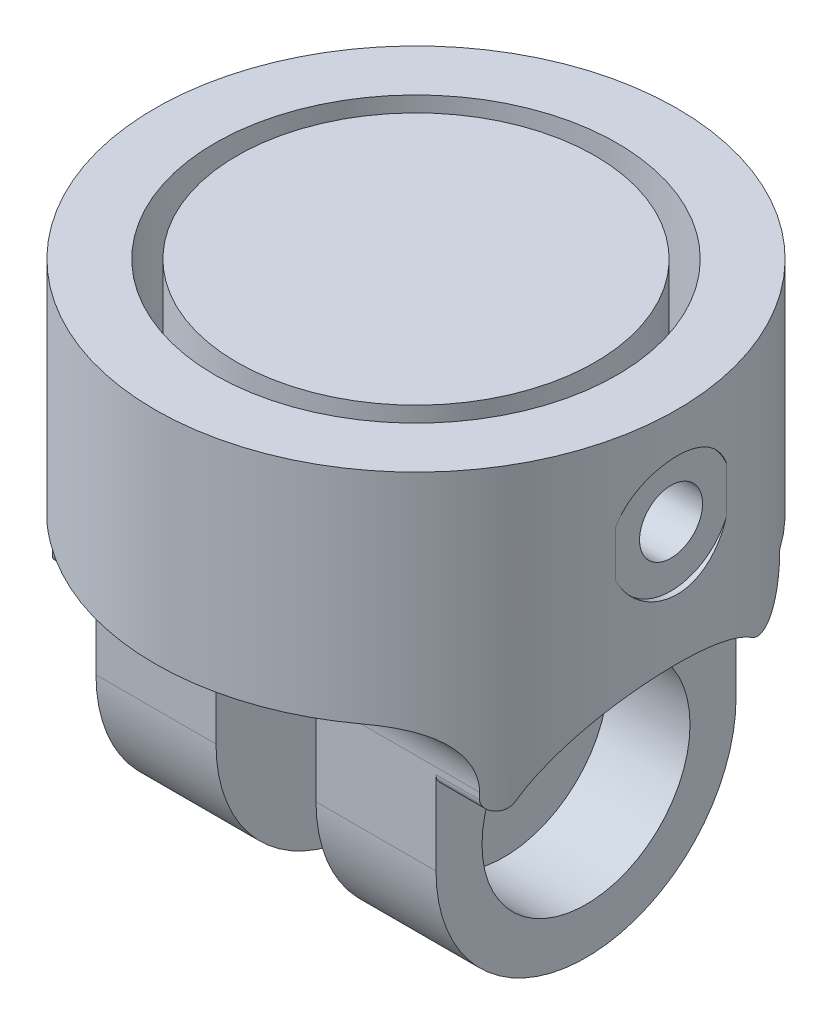
SolidWorks part; units mm, degrees
material "PLA Black"
ref_plane "Front" through (0, 0, 0) normal (0, 0, 1) x (1, 0, 0)
ref_plane "Top" through (0, 0, 0) normal (0, 1, 0) x (1, 0, 0)
ref_plane "Right" through (0, 0, 0) normal (1, 0, 0) x (0, 0, -1)
sketch "Sketch1" plane through (0, 0, 0) normal (0, 1, 0) x (1, 0, 0)
  line L0 (0, 8.95) -> (0, 10.05) construction
  circle A0 centre (0, 0) radius 10.05
  circle A1 centre (0, 0) radius 13.05
  circle A2 centre (0, 0) radius 9.5 construction
  circle A4 centre (0, 0) radius 8.95
  point P11 (0, 9.5)
  dimension "D1" = 1.1
  dimension "D2" = 3
  dimension "D3" = 19
extrude "Boss-Extrude1" add sketch "Sketch1" along normal blind 10 contours A1 A0 | A4 region at (-12.6809, 0, 0) region at (0, 0, 0)
sketch "Sketch3" plane through (0, 0, 0) normal (0, -1, 0) x (1, 0, 0)
  circle A2 centre (0, 0) radius 13.05 construction
  circle A3 centre (0, 0) radius 13.05
extrude "Boss-Extrude2" add sketch "Sketch3" along normal blind 1
sketch "Sketch4" plane through (0, -1, 0) normal (0, -1, 0) x (1, 0, 0)
  line L0 (0, 17.8908) -> (0, -17.0763) construction
  line L1 (2.5, 7.5) -> (8.5, 7.5)
  line L2 (2.5, 7.5) -> (2.5, -7.5)
  line L3 (2.5, -7.5) -> (8.5, -7.5)
  line L4 (8.5, 7.5) -> (8.5, -7.5)
  line L5 (-8.5, 7.5) -> (-8.5, -7.5)
  line L6 (-2.5, -7.5) -> (-8.5, -7.5)
  line L7 (-2.5, 7.5) -> (-2.5, -7.5)
  line L8 (-2.5, 7.5) -> (-8.5, 7.5)
  line L9 (16.8049, 0) -> (-19.8998, 0) construction
  dimension "D1" = 6
  dimension "D2" = 5
  dimension "D3" = 15
extrude "Boss-Extrude3" add sketch "Sketch4" along normal blind 15
sketch "Sketch5" plane through (8.5, 0, 0) normal (1, 0, 0) x (0, 0, -1)
  line L0 (-7.5, -16) -> (-7.5, -1) construction
  line L1 (7.5, -16) -> (7.5, -1) construction
  line L2 (7.5, -8.5) -> (7.5, -17.1619)
  line L3 (7.5, -17.1619) -> (-7.5, -17.1619)
  line L4 (-7.5, -17.1619) -> (-7.5, -8.5)
  arc A0 (-7.5, -8.5) -> (7.5, -8.5) centre (0, -8.5) ccw
  circle A1 centre (0, -8.5) radius 1.55
  dimension "D1" = 3.1
extrude "Cut-Extrude1" cut sketch "Sketch5" against normal through all both and the other way through all
sketch "Sketch6" plane through (8.5, 0, 0) normal (1, 0, 0) x (0, 0, -1)
  circle A0 centre (0, -8.5) radius 5.2
  dimension "D1" = 10.4
extrude "Cut-Extrude2" cut sketch "Sketch6" against normal blind 4.1
mirror "Mirror1" about plane through (0, 0, 0) normal (1, 0, 0) of "Cut-Extrude2"
ref_plane "Plane9" through (1.335, 0, 0) normal (1, 0, 0) x (0, 0, -1)
sketch "Sketch7" plane through (1.335, 0, 0) normal (1, 0, 0) x (0, 0, -1)
  line L0 (3.555, -8.5) -> (3.555, -1) construction
  line L1 (7.5, -1) -> (-7.5, -1) construction
  line L2 (3.4474, -7.632) -> (1.7775, -1) construction
  line L3 (3.1303, -6.8149) -> (0, -1) construction
  line L4 (1.7775, -0.6757) -> (1.7775, -1.4422) construction
  line L5 (2.6911, -6.1771) -> (-1.7775, -1) construction
  line L6 (2.2506, -5.7481) -> (-3.555, -1) construction
  line L8 (0, -1.6788) -> (0, 0) construction
  line L9 (-8.4824, -8.5) -> (8.712, -8.5) construction
  line L10 (1.8766, -5.4807) -> (-5.3325, -1) construction
  line L11 (-3.555, -0.3587) -> (-3.555, -1.6788) construction
  circle A0 centre (0, -8.5) radius 3.555 construction
  dimension "D1" = 7.11
  dimension "D2" = 31.862
  dimension "D3" = 7.5
ref_plane "Plane1" through (1.335, -1, -3.555) normal (0, 1, 0) x (1, 0, 0)
ref_plane "Plane2" through (1.335, -1, -1.7775) normal (0, 0.9697, 0.2442) x (1, 0, 0)
ref_plane "Plane3" through (1.335, -1, 0) normal (0, 0.8805, 0.474) x (1, 0, 0)
ref_plane "Plane5" through (1.335, -1, 1.7775) normal (0, 0.757, 0.6534) x (1, 0, 0)
ref_plane "Plane6" through (1.335, -1, 3.555) normal (0, 0.6331, 0.7741) x (1, 0, 0)
ref_plane "Plane7" through (1.335, -1, 5.3325) normal (0, 0.5279, 0.8493) x (1, 0, 0)
sketch "Sketch8" plane through (1.335, -1, -3.555) normal (0, 1, 0) x (1, 0, 0)
  circle A0 centre (0, 0) radius 0.4895
  dimension "D1" = 0.979
extrude "Cut-Extrude5" cut sketch "Sketch8" along normal blind 5.5 and the other way through all
sketch "Sketch9" plane through (1.335, -1, -1.7775) normal (0, 0.9697, 0.2442) x (1, 0, 0)
  circle A0 centre (0, 0) radius 0.4895
  dimension "D1" = 0.979
extrude "Cut-Extrude3" cut sketch "Sketch9" along normal blind 5.5
sketch "Sketch10" plane through (1.335, -1, 0) normal (0, 0.8805, 0.474) x (1, 0, 0)
  circle A0 centre (0, 0) radius 0.4895
  dimension "D1" = 0.979
sketch "Sketch11" plane through (1.335, -1, 1.7775) normal (0, 0.757, 0.6534) x (1, 0, 0)
  circle A0 centre (0, 0) radius 0.4895
  dimension "D1" = 0.979
sketch "Sketch12" plane through (1.335, -1, 3.555) normal (0, 0.6331, 0.7741) x (1, 0, 0)
  circle A0 centre (0, 0) radius 0.4895
  dimension "D1" = 0.979
sketch "Sketch14" plane through (1.335, -1, 5.3325) normal (0, 0.5279, 0.8493) x (1, 0, 0)
  circle A0 centre (0, 0) radius 0.4895
  dimension "D1" = 0.979
extrude "Cut-Extrude6" cut sketch "Sketch10" along normal blind 5.5 and the other way through all
extrude "Cut-Extrude7" cut sketch "Sketch11" along normal blind 5.5 and the other way through all contours A0
extrude "Cut-Extrude8" cut sketch "Sketch12" along normal blind 5.5 and the other way through all contours A0
extrude "Cut-Extrude9" cut sketch "Sketch14" along normal blind 5.5 and the other way through all contours A0
ref_plane "Plane8" through (13.05, 0, 0) normal (1, 0, 0) x (0, 0, -1)
hole_wizard "Tap Drill for M3 Helicoil1" positions "Sketch17" profile "Sketch18" hole size "M3x0.5" standard "DIN"
sketch "Sketch17" plane through (13.05, 0, 0) normal (1, 0, 0) x (0, 0, -1)
  line L0 (-22.2973, 5) -> (18.0703, 5) construction
  line L4 (0, 12.2732) -> (0, -5.3405) construction
  line L6 (-7.5, -8.5) -> (-7.5, -1) construction
  line L7 (7.5, -8.5) -> (7.5, -1) construction
  line L8 (13.05, 10) -> (-13.05, 10) construction
  line L9 (10.05, 0) -> (-10.05, 0) construction
  point P0 (0, 5)
sketch "Sketch18" plane through (13.05, 5, 0) normal (0, 1, 0) x (0, 0, -1)
  line L0 (0, 0) -> (0, 6.9464)
  line L1 (0, 6.9464) -> (1.575, 6)
  line L2 (1.575, 6) -> (1.575, 0)
  line L5 (1.575, 0) -> (0, 0)
  line L10 (0, 6.9464) -> (-1.575, 6) construction
  line L11 (0, -6.35) -> (0, 107.95) construction
  dimension "Hole Dia." = 3.15
  dimension "Hole Depth" = 6
  dimension "Drill Angle" = 118
sketch "Sketch20" plane through (13.05, 0, 0) normal (1, 0, 0) x (0, 0, -1)
  circle A0 centre (0, 5) radius 3
  dimension "D1" = 6
extrude "Cut-Extrude10" cut sketch "Sketch20" against normal blind 0.3
sketch "Sketch21" plane through (8.5, 0, 0) normal (1, 0, 0) x (0, 0, -1)
  line L0 (7.5, -1) -> (-7.5, -1) construction
  line L1 (7.5, -0.1252) -> (7.5, -1.1767)
  line L2 (0.9244, -19.0662) -> (-4.8209, -14.2453) construction
  line L3 (0, 5.2718) -> (0, -9.2894) construction
  line L4 (0, 10) -> (0, -1) construction
  line L5 (-7.5, -0.1252) -> (-7.5, -4.3226)
  line L6 (7.5, -0.1252) -> (-7.5, -0.1252)
  line L7 (-7.5, -8.5) -> (-7.5, -1) construction
  line L8 (7.5, -8.5) -> (7.5, -1) construction
  line L9 (0, -1) -> (9.4693, -4.4465) construction
  line L10 (0, -1) -> (1.6171, -0.0664) construction
  line L11 (4.6128, -2.5863) -> (7.5, -1.1767) construction
  line L12 (10.5662, -7.5756) -> (4.8209, -2.7547) construction
  line L13 (-4.8209, -14.2453) -> (4.8209, -2.7547) construction
  line L14 (10.5662, -7.5756) -> (0.9244, -19.0662) construction
  arc A0 (-6.4204, -4.6233) -> (4.6128, -2.5863) centre (0, -8.5) cw
  arc A1 (-6.4204, -4.6233) -> (-7.5, -4.3226) centre (-6.9183, -4.3226) cw
  arc A2 (7.5, -1.1767) -> (4.6128, -2.5863) centre (5.7123, -1.1767) cw
  circle A3 centre (0, -8.5) radius 1.55 construction
  arc A4 (-4.8209, -14.2453) -> (4.8209, -2.7547) centre (0, -8.5) cw construction
  dimension "D1" = 30
  dimension "D3" = 7.5
  dimension "D2" = 50
  dimension "D4" = 15
extrude "Boss-Extrude4" add sketch "Sketch21" along normal up to surface (2.1795 mm away) up to face at (12.895, 5, 0)
mirror "Mirror2" about plane through (0, 0, 0) normal (1, 0, 0) of "Boss-Extrude4", "Tap Drill for M3 Helicoil1", "Cut-Extrude10"
fillet "Fillet1" radius 3 2 edges at (-6.5898, -1, 7.5) (6.5898, -1, 7.5)
equation "\"knee_angle\"= 70"
equation "\"ankle_angle\" = 80"
equation "\"hip_angle\" = 40"
equation "\"spring_ankle_parallel_arm_diameter\"= 0.89"
equation "\"spring_ankle_parallel_arm_length\"= 13"
equation "\"spring_ankle_parallel_intern_diameter\"= 6.22"
equation "\"spring_ankle_parallel_angle\"= \"ankle_angle\""
equation "\"spring_ankle_parallel_turns\"= 3"
equation "\"spring_ankle_parallel_pitch\"= \"spring_ankle_parallel_arm_diameter\" * 1.01"
equation "\"spring_ankle_parallel_cutting_distance\"= (1-\"spring_ankle_parallel_angle\" / 360) * \"spring_ankle_parallel_pitch\""
equation "\"spring_ankle_serial_arm_diameter\"= 0.89"
equation "\"spring_ankle_serial_arm_length\"= 10"
equation "\"spring_ankle_serial_intern_diameter\"= 6.22"
equation "\"spring_ankle_serial_angle\"= \"90\""
equation "\"spring_ankle_serial_turns\"= 3"
equation "\"spring_ankle_serial_pitch\"= \"spring_ankle_serial_arm_diameter\" * 1.01"
equation "\"spring_ankle_serial_cutting_distance\"= (1-\"spring_ankle_serial_angle\" / 360) * \"spring_ankle_serial_pitch\""
equation "\"spring_knee_parallel_arm_diameter\"= 0.89"
equation "\"spring_knee_parallel_arm_length\"= 15"
equation "\"spring_knee_parallel_intern_diameter\"= 5.46"
equation "\"spring_knee_parallel_angle\"= -\"knee_angle\" + 90"
equation "\"spring_knee_parallel_turns\"= 3"
equation "\"spring_knee_parallel_pitch\"= \"spring_knee_parallel_arm_diameter\" * 1.01"
equation "\"spring_knee_parallel_cutting_distance\"= (1-(\"spring_knee_parallel_angle\") / 360) * \"spring_knee_parallel_pitch\""
equation "\"spring_knee_serial_arm_diameter\"= 0.89"
equation "\"spring_knee_serial_arm_length\"= 10"
equation "\"spring_knee_serial_intern_diameter\"= 5.46"
equation "\"spring_knee_serial_angle\"= \"90\""
equation "\"spring_knee_serial_turns\"= 3"
equation "\"spring_knee_serial_pitch\"= \"spring_knee_serial_arm_diameter\" * 1.01"
equation "\"spring_knee_serial_cutting_distance\"= (1-\"spring_knee_serial_angle\" / 360) * \"spring_knee_serial_pitch\""
equation "\"spring_ankle_parallel_nominal_diameter\"= \"spring_ankle_parallel_arm_diameter\" + \"spring_ankle_parallel_intern_diameter\""
equation "\"spring_ankle_serial_nominal_diameter\"= \"spring_ankle_serial_arm_diameter\" + \"spring_ankle_serial_intern_diameter\""
equation "\"spring_knee_parallel_nominal_diameter\"= \"spring_knee_parallel_arm_diameter\" + \"spring_knee_parallel_intern_diameter\""
equation "\"spring_knee_serial_nominal_diameter\"= \"spring_knee_serial_arm_diameter\" + \"spring_knee_serial_intern_diameter\""
equation "\"D1@Sketch7\"=\"spring_ankle_parallel_nominal_diameter\""
equation "\"D1@Sketch8\"=\"spring_ankle_parallel_arm_diameter\"*1.1"
equation "\"D1@Sketch9\"=\"spring_ankle_parallel_arm_diameter\"*1.1"
equation "\"D1@Sketch10\"=\"spring_ankle_parallel_arm_diameter\"*1.1"
equation "\"D1@Sketch11\"=\"spring_ankle_parallel_arm_diameter\"*1.1"
equation "\"D1@Sketch12\"=\"spring_ankle_parallel_arm_diameter\"*1.1"
equation "\"D1@Sketch14\"=\"spring_ankle_parallel_arm_diameter\"*1.1"
equation "\"D1@Cut-Extrude3\"=\"spring_ankle_parallel_arm_length\"-\"axis_structure_distance\""
equation "\"axis_structure_distance\"= 7.5"
equation "\"D1@Cut-Extrude5\"=\"spring_ankle_parallel_arm_length\"-\"axis_structure_distance\""
equation "\"D1@Cut-Extrude6\"=\"spring_ankle_parallel_arm_length\"-\"axis_structure_distance\""
equation "\"D1@Cut-Extrude7\"=\"spring_ankle_parallel_arm_length\"-\"axis_structure_distance\""
equation "\"D1@Cut-Extrude8\"=\"spring_ankle_parallel_arm_length\"-\"axis_structure_distance\""
equation "\"D1@Cut-Extrude9\"=\"spring_ankle_parallel_arm_length\"-\"axis_structure_distance\""
equation "\"D1@Boss-Extrude3\"=\"axis_structure_distance\"*2"
equation "\"ankle_angle_max\" = 120"
equation "\"ankle_angle_min\" = 50"
equation "\"knee_angle_max\" = 120"
equation "\"knee_angle_min\" = 0"
equation "\"hip_angle_max\" = 90"
equation "\"hip_angle_min\" = -60"
equation "\"D1@Sketch21\"=\"ankle_angle_max\"-90"
equation "\"D2@Sketch21\"=\"ankle_angle_min\""
equation "\"D1@Plane9\"=(\"spring_ankle_parallel_arm_diameter\"*\"spring_ankle_parallel_turns\")/2"
